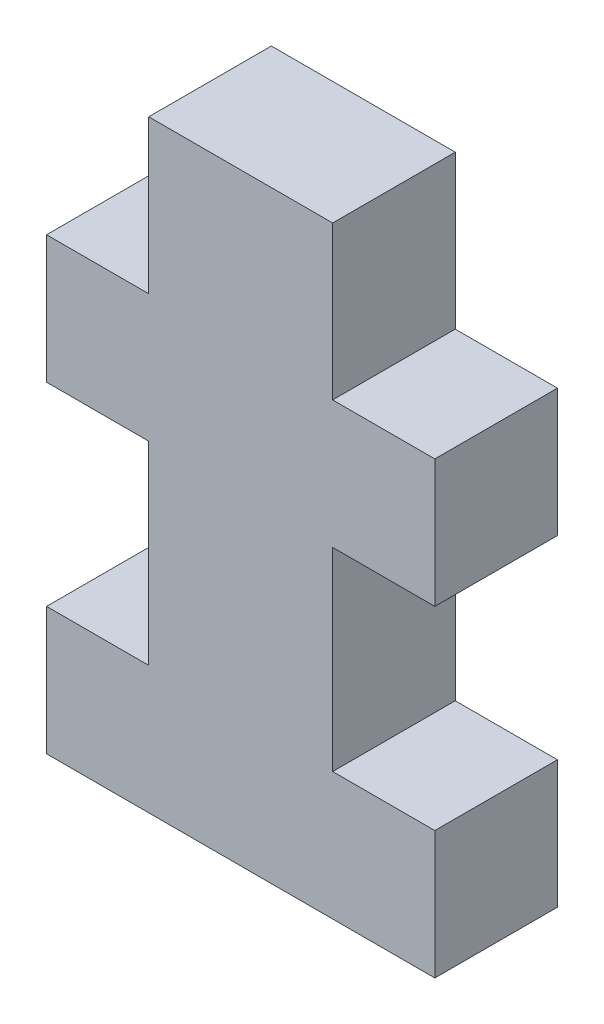
SolidWorks part; units mm, degrees
ref_plane "Front" through (0, 0, 0) normal (0, 0, 1) x (1, 0, 0)
ref_plane "Top" through (0, 0, 0) normal (0, 1, 0) x (1, 0, 0)
ref_plane "Right" through (0, 0, 0) normal (1, 0, 0) x (0, 0, -1)
ref_axis "side-side" through (80.9, 0, 0) along (-1, 0, 0)
ref_axis "up-down" through (0, 50, 0) along (0, -1, 0)
ref_axis "front-back" through (0, 0, -80.9) along (0, 0, 1)
sketch "Sketch1" plane through (0, 0, 0) normal (0, 0, 1) x (1, 0, 0)
  line L0 (4.572, 50.546) -> (4.572, 70.866) construction
  line L1 (4.572, 61.976) -> (4.572, 71.628)
  line L2 (-4.572, 50.546) -> (-4.572, 70.866) construction
  line L3 (-4.572, 61.976) -> (-4.572, 71.628)
  line L4 (4.572, 55.626) -> (-4.572, 55.626) construction
  line L5 (9.652, 55.626) -> (-9.652, 55.626)
  line L6 (4.572, 85.598) -> (-4.572, 85.598)
  line L7 (9.652, 61.976) -> (4.572, 61.976)
  line L8 (9.652, 61.976) -> (9.652, 55.626)
  line L9 (9.652, 77.978) -> (4.572, 77.978)
  line L10 (-9.652, 61.976) -> (-9.652, 55.626)
  line L11 (9.652, 77.978) -> (9.652, 71.628)
  line L12 (9.652, 71.628) -> (4.572, 71.628)
  line L13 (-9.652, 77.978) -> (-9.652, 71.628)
  line L14 (4.572, 77.978) -> (4.572, 85.598)
  line L15 (-4.572, 77.978) -> (-4.572, 85.598)
  line L16 (-4.572, 71.628) -> (-9.652, 71.628)
  line L17 (-4.572, 61.976) -> (-9.652, 61.976)
  line L18 (-4.572, 77.978) -> (-9.652, 77.978)
  dimension "D1" = 5.08
  dimension "D2" = 5.08
  dimension "D3" = 6.35
  dimension "D4" = 7.62
  dimension "D5" = 6.35
extrude "Boss-Extrude1" add sketch "Sketch1" along normal mid plane 6.096
